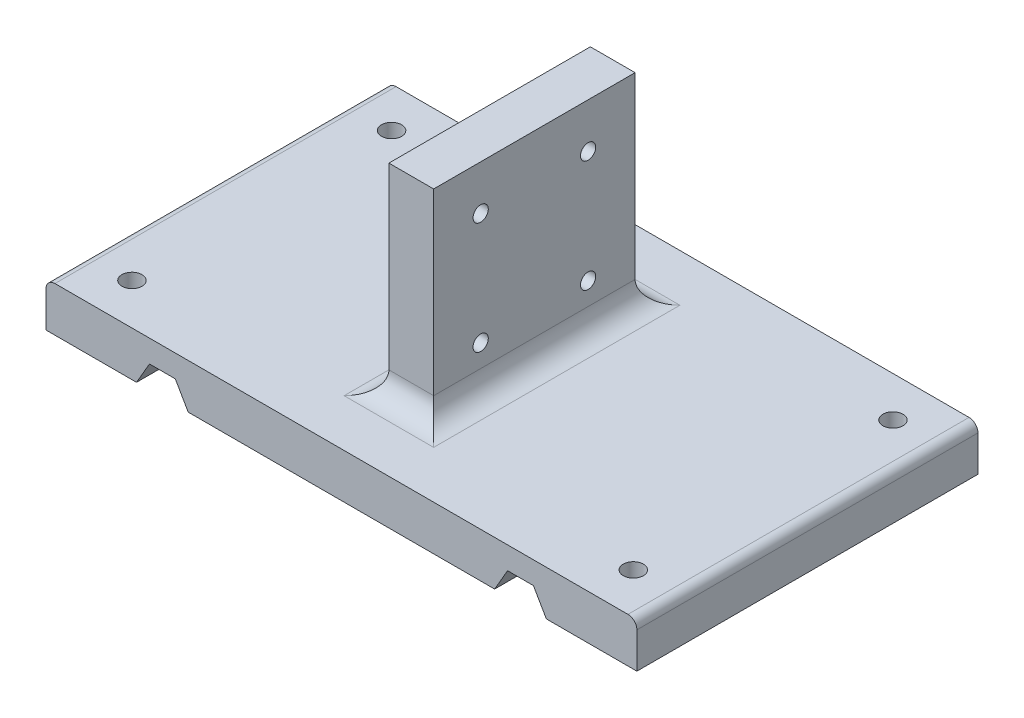
SolidWorks part; units mm, degrees
ref_plane "Front Plane" through (0, 0, 0) normal (0, 0, 1) x (1, 0, 0)
ref_plane "Top Plane" through (0, 0, 0) normal (0, 1, 0) x (1, 0, 0)
ref_plane "Right Plane" through (0, 0, 0) normal (1, 0, 0) x (0, 0, -1)
sketch "Sketch1" plane through (0, 0, 0) normal (0, 0, 1) x (1, 0, 0)
  line L1 (-66, 0) -> (66, 0)
  line L2 (-66, 0) -> (-66, 10)
  line L3 (-66, 10) -> (66, 10)
  line L4 (66, 0) -> (66, 10)
  point P4 (0, 0)
  dimension "D1" = 132
  dimension "D2" = 10
extrude "Boss-Extrude1" add sketch "Sketch1" along normal blind 76.2 contours L3 L4 L1 L2
sketch "Sketch2" plane through (0, 0, 76.2) normal (0, 0, 1) x (1, 0, 0)
  line L0 (-66, 0) -> (66, 0) construction
  line L7 (0, 0) -> (0, 19.3508) construction
  line L8 (34.2265, 0) -> (37.1132, -5)
  line L9 (37.1132, -5) -> (42.8868, -5)
  line L10 (42.8868, -5) -> (45.7735, 0)
  line L11 (45.7735, 0) -> (42.8868, 5)
  line L12 (42.8868, 5) -> (37.1132, 5)
  line L13 (37.1132, 5) -> (34.2265, 0)
  line L14 (-37.1132, 5) -> (-34.2265, 0)
  line L15 (-66, 0) -> (-66, 10) construction
  line L16 (-42.8868, 5) -> (-37.1132, 5)
  line L17 (-45.7735, 0) -> (-42.8868, 5)
  line L18 (-42.8868, -5) -> (-45.7735, 0)
  line L19 (-37.1132, -5) -> (-42.8868, -5)
  line L20 (-34.2265, 0) -> (-37.1132, -5)
  circle A0 centre (-40, 0) radius 5 construction
  circle A1 centre (40, 0) radius 5 construction
  dimension "D2" = 10
  dimension "D4" = 40
extrude "Cut-Extrude1" cut sketch "Sketch2" against normal blind 76.2
sketch "Sketch11" plane through (0, 10, 0) normal (0, 1, 0) x (1, 0, 0)
  line L0 (-66, -76.2) -> (-66, 0) construction
  line L1 (66, -76.2) -> (66, 0) construction
  line L2 (-66, 0) -> (66, 0) construction
  circle A0 centre (-56, -9) radius 4
  circle A1 centre (-56, -67) radius 4
  circle A2 centre (56, -9) radius 4
  circle A3 centre (56, -67) radius 4
  dimension "D1" = 8
  dimension "D2" = 10
  dimension "D3" = 10
  dimension "D4" = 9
  dimension "D5" = 9
  dimension "D6" = 58
fillet "Fillet2" radius 2 2 edges at (66, 10, 38.1) (-66, 10, 38.1)
hole_wizard "M4 Clearance Hole1" positions "Sketch12" profile "Sketch13" hole size "M4" standard "ANSI Metric" end condition through all
sketch "Sketch12" plane through (0, 10, 0) normal (0, 1, 0) x (1, 0, 0)
  point P0 (-56, -67)
  point P3 (-56, -9)
  point P6 (56, -9)
  point P9 (56, -67)
sketch "Sketch13" plane through (-56, 10, 67) normal (1, 0, 0) x (0, 0, 1)
  line L0 (0, 0) -> (0, 10)
  line L1 (0, 10) -> (2.25, 10)
  line L2 (2.25, 10) -> (2.25, 0)
  line L5 (2.25, 0) -> (0, 0)
  line L11 (0, -6.35) -> (0, 107.95) construction
  dimension "Thru Hole Dia." = 4.5
  dimension "Thru Hole Depth" = 10
sketch "Sketch14" plane through (0, 10, 0) normal (0, 1, 0) x (1, 0, 0)
  line L0 (0, 0) -> (0, -76.2) construction
  line L1 (-64, -76.2) -> (64, -76.2) construction
  line L3 (-5, -60.6) -> (5, -60.6)
  line L4 (-5, -60.6) -> (-5, -15.6)
  line L5 (-5, -15.6) -> (5, -15.6)
  line L6 (5, -60.6) -> (5, -15.6)
  line L7 (-5, -60.6) -> (5, -15.6) construction
  line L8 (-5, -15.6) -> (5, -60.6) construction
  point P5 (0, -38.1)
  dimension "D1" = 45
  dimension "D2" = 10
extrude "Boss-Extrude2" add sketch "Sketch14" along normal blind 45
sketch "Sketch15" plane through (-5, 0, 18.1) normal (1, 0, 0) x (0, 0, -1)
  line L0 (-20, 32.5) -> (-20, 20) construction
  line L1 (-35, 20) -> (-5, 20) construction
  line L2 (-35, 20) -> (-35, 45) construction
  line L3 (-35, 45) -> (-5, 45) construction
  line L4 (-5, 20) -> (-5, 45) construction
  line L5 (-35, 20) -> (-5, 45) construction
  line L6 (-35, 45) -> (-5, 20) construction
  line L7 (-20, 32.5) -> (-5, 32.5) construction
  line L8 (-34.25, 35.5) -> (-35.75, 35.5)
  line L9 (-5.75, 29.5) -> (-4.25, 29.5)
  line L10 (-5.75, 29.5) -> (-5.75, 35.5)
  line L11 (-5.75, 35.5) -> (-4.25, 35.5)
  line L12 (-4.25, 29.5) -> (-4.25, 35.5)
  line L13 (-5.75, 29.5) -> (-4.25, 35.5) construction
  line L14 (-5.75, 35.5) -> (-4.25, 29.5) construction
  line L15 (-35.75, 29.5) -> (-35.75, 35.5)
  line L16 (-34.25, 29.5) -> (-35.75, 29.5)
  line L17 (-34.25, 29.5) -> (-34.25, 35.5)
  line L18 (-20, 55) -> (-20, 10) construction
  line L19 (-32, 20) -> (-8, 20) construction
  line L20 (-32, 20) -> (-32, 45) construction
  line L21 (-32, 45) -> (-8, 45) construction
  line L22 (-8, 20) -> (-8, 45) construction
  line L23 (-32, 20) -> (-8, 45) construction
  line L24 (-32, 45) -> (-8, 20) construction
  line L25 (2.5, 55) -> (-42.5, 55) construction
  line L26 (2.5, 10) -> (-42.5, 10) construction
  line L29 (2.5, 32.5) -> (-42.5, 32.5) construction
  line L30 (2.5, 55) -> (2.5, 10) construction
  line L31 (-42.5, 55) -> (-42.5, 10) construction
  circle A0 centre (-32, 45) radius 3
  circle A1 centre (-8, 45) radius 3
  circle A2 centre (-8, 20) radius 3
  circle A3 centre (-32, 20) radius 3
  point P21 (-32, 20)
  point P23 (-32, 45)
  point P25 (-8, 45)
  point P27 (-8, 20)
  point P39 (-20, 36)
  dimension "D7" = 6
  dimension "D1" = 30
  dimension "D2" = 25
  dimension "D3" = 6
  dimension "D4" = 1.5
  dimension "D5" = 24
  dimension "D6" = 25
extrude "Boss-Extrude3" add sketch "Sketch15" against normal blind 4.4
sketch "Sketch16" plane through (-9.4, 0, 0) normal (-1, 0, 0) x (0, 0, 1)
  point P0 (50.1, 45)
  point P1 (26.1, 45)
  point P3 (26.1, 20)
  point P5 (50.1, 20)
hole_wizard "Ø3.0mm Dowel Hole1" positions "Sketch19" profile "Sketch18" hole size "Ø3.0" standard "ANSI Metric" end condition through all
sketch "Sketch19" plane through (-9.4, 0, 0) normal (-1, 0, 0) x (0, 0, 1)
  point P0 (50.1, 45)
  point P3 (26.1, 45)
  point P6 (26.1, 20)
  point P9 (50.1, 20)
sketch "Sketch18" plane through (-9.4, 45, 50.1) normal (0, 1, 0) x (0, 0, 1)
  line L0 (0, 0) -> (0, 75.4)
  line L1 (0, 75.4) -> (1.7, 75.4)
  line L2 (1.7, 75.4) -> (1.7, 0)
  line L5 (1.7, 0) -> (0, 0)
  line L11 (0, -6.35) -> (0, 107.95) construction
  dimension "Thru Hole Dia." = 3.4
  dimension "Thru Hole Depth" = 75.4
sketch "Sketch20" plane through (-9.4, 0, 0) normal (-1, 0, 0) x (0, 0, 1)
  line L0 (50.1, 45) -> (48.4, 45) construction
  line L6 (45.8, 45) -> (46.2, 45) construction
  line L7 (46.2, 49) -> (48, 49)
  line L8 (48, 49) -> (48, 41)
  line L9 (48, 41) -> (46.2, 41)
  line L10 (46.2, 49) -> (46.2, 41)
  line L11 (48, 45) -> (48.4, 45) construction
  circle A2 centre (50.1, 45) radius 1.7 construction
  dimension "D4" = 0.4
  dimension "D5" = 1.8
  dimension "D6" = 8
  dimension "D7" = 0.4
extrude "Cut-Extrude3" cut sketch "Sketch20" against normal up to surface (4.4 mm away) up to face at (-5, 20, 53.1)
fillet "Fillet3 - 2mm" radius 2 4 edges at (-5, 20, 23.1) (-5, 20, 53.1) (-5, 45, 53.1) (-5, 45, 29.1)
fillet "Fillet4 - 1mm" radius 1 9 edges at (-5, 45, 48) (-5, 29.5, 53.1) (-5, 32.5, 52.35) (-5, 32.5, 53.85) (-5, 35.5, 53.1) (-5, 35.5, 23.1) (-5, 32.5, 23.85) (-5, 29.5, 23.1) (-5, 32.5, 22.35)
fillet "Fillet5" radius 5 4 edges at (0, 10, 60.6) (5, 10, 38.1) (0, 10, 15.6) (-5, 10, 38.1)
